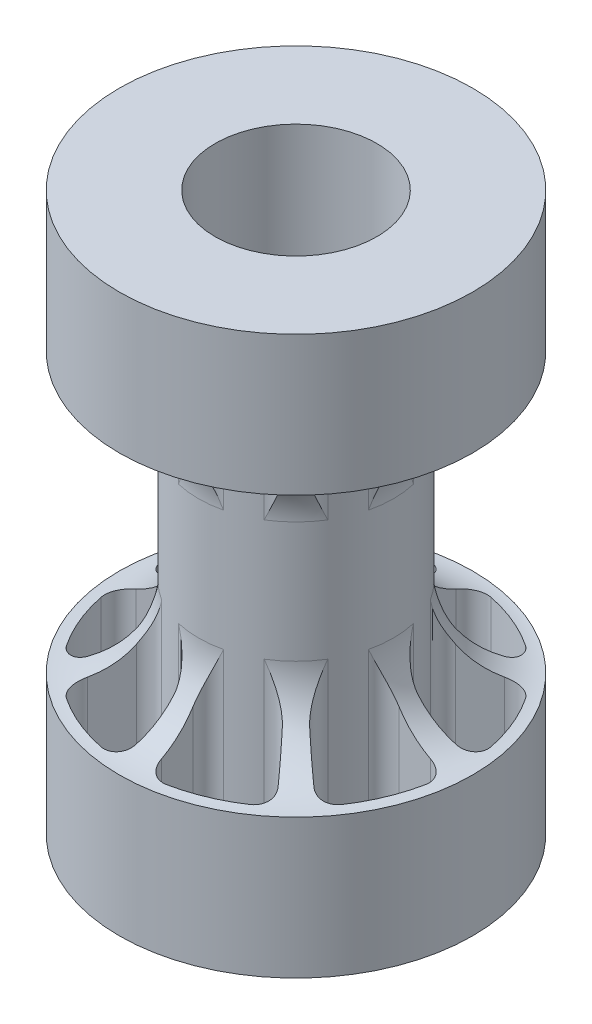
SolidWorks part; units mm, degrees
material "CA"
ref_plane "Front Plane" through (0, 0, 0) normal (0, 0, 1) x (1, 0, 0)
ref_plane "Top Plane" through (0, 0, 0) normal (0, 1, 0) x (1, 0, 0)
ref_plane "Right Plane" through (0, 0, 0) normal (1, 0, 0) x (0, 0, -1)
sketch "Sketch1" plane through (0, 0, 0) normal (0, 1, 0) x (1, 0, 0)
  circle A0 centre (0, 0) radius 14.5
  circle A1 centre (0, 0) radius 17.5
  dimension "D1" = 29
  dimension "D2" = 3
extrude "Boss-Extrude1" add sketch "Sketch1" along normal blind 100
sketch "Sketch2" plane through (0, 0, 0) normal (0, -1, 0) x (1, 0, 0)
  line L3 (-1.5, 17.4356) -> (-2.2728, 26.4182)
  line L6 (1.5, 17.4356) -> (2.2728, 26.4182)
  line L7 (11.2682, 13.3895) -> (17.0734, 20.2876)
  line L8 (13.3895, 11.2682) -> (20.2876, 17.0734)
  line L9 (17.4356, 1.5) -> (26.4182, 2.2728)
  line L10 (17.4356, -1.5) -> (26.4182, -2.2728)
  line L11 (13.3895, -11.2682) -> (20.2876, -17.0734)
  line L12 (11.2682, -13.3895) -> (17.0734, -20.2876)
  line L13 (1.5, -17.4356) -> (2.2728, -26.4182)
  line L14 (-1.5, -17.4356) -> (-2.2728, -26.4182)
  line L15 (-11.2682, -13.3895) -> (-17.0734, -20.2876)
  line L16 (-13.3895, -11.2682) -> (-20.2876, -17.0734)
  line L17 (-17.4356, -1.5) -> (-26.4182, -2.2728)
  line L18 (-17.4356, 1.5) -> (-26.4182, 2.2728)
  line L19 (-13.3895, 11.2682) -> (-20.2876, 17.0734)
  line L20 (-11.2682, 13.3895) -> (-17.0734, 20.2876)
  circle A0 centre (0, 0) radius 31.685
  arc A1 (-24.7173, 16.4395) -> (-29.1022, 5.8533) centre (0, 0) ccw
  circle A2 centre (0, 0) radius 17.5 construction
  arc A3 (-11.2682, 13.3895) -> (-13.3895, 11.2682) centre (0, 0) ccw
  arc A4 (1.5, 17.4356) -> (-1.5, 17.4356) centre (0, 0) ccw
  arc A5 (13.3895, 11.2682) -> (11.2682, 13.3895) centre (0, 0) ccw
  arc A6 (17.4356, -1.5) -> (17.4356, 1.5) centre (0, 0) ccw
  arc A7 (11.2682, -13.3895) -> (13.3895, -11.2682) centre (0, 0) ccw
  arc A8 (-1.5, -17.4356) -> (1.5, -17.4356) centre (0, 0) ccw
  arc A9 (-13.3895, -11.2682) -> (-11.2682, -13.3895) centre (0, 0) ccw
  arc A10 (-17.4356, 1.5) -> (-17.4356, -1.5) centre (0, 0) ccw
  arc A11 (-5.8533, 29.1022) -> (-16.4395, 24.7173) centre (0, 0) ccw
  arc A12 (16.4395, 24.7173) -> (5.8533, 29.1022) centre (0, 0) ccw
  arc A13 (29.1022, 5.8533) -> (24.7173, 16.4395) centre (0, 0) ccw
  arc A14 (24.7173, -16.4395) -> (29.1022, -5.8533) centre (0, 0) ccw
  arc A15 (5.8533, -29.1022) -> (16.4395, -24.7173) centre (0, 0) ccw
  arc A16 (-16.4395, -24.7173) -> (-5.8533, -29.1022) centre (0, 0) ccw
  arc A17 (-29.1022, -5.8533) -> (-24.7173, -16.4395) centre (0, 0) ccw
  arc A18 (26.4182, 2.2728) -> (29.1022, 5.8533) centre (26.1611, 5.2617) ccw
  arc A19 (26.4182, -2.2728) -> (29.1022, -5.8533) centre (26.1611, -5.2617) cw
  arc A20 (20.2876, -17.0734) -> (24.7173, -16.4395) centre (22.2193, -14.7781) ccw
  arc A21 (17.0734, -20.2876) -> (16.4395, -24.7173) centre (14.7781, -22.2193) cw
  arc A22 (2.2728, -26.4182) -> (5.8533, -29.1022) centre (5.2617, -26.1611) ccw
  arc A23 (-2.2728, -26.4182) -> (-5.8533, -29.1022) centre (-5.2617, -26.1611) cw
  arc A24 (-17.0734, -20.2876) -> (-16.4395, -24.7173) centre (-14.7781, -22.2193) ccw
  arc A25 (-20.2876, -17.0734) -> (-24.7173, -16.4395) centre (-22.2193, -14.7781) cw
  arc A26 (-26.4182, -2.2728) -> (-29.1022, -5.8533) centre (-26.1611, -5.2617) ccw
  arc A27 (-26.4182, 2.2728) -> (-29.1022, 5.8533) centre (-26.1611, 5.2617) cw
  arc A28 (-20.2876, 17.0734) -> (-24.7173, 16.4395) centre (-22.2193, 14.7781) ccw
  arc A29 (-17.0734, 20.2876) -> (-16.4395, 24.7173) centre (-14.7781, 22.2193) cw
  arc A30 (20.2876, 17.0734) -> (24.7173, 16.4395) centre (22.2193, 14.7781) cw
  arc A31 (17.0734, 20.2876) -> (16.4395, 24.7173) centre (14.7781, 22.2193) ccw
  arc A32 (2.2728, 26.4182) -> (5.8533, 29.1022) centre (5.2617, 26.1611) cw
  arc A33 (-2.2728, 26.4182) -> (-5.8533, 29.1022) centre (-5.2617, 26.1611) ccw
  point P41 (0, 0)
  point P49 (0, 0)
  point P72 (-2.5444, 29.5758)
  dimension "D1" = 63.37
  dimension "D2" = 2
  dimension "D6" = 3
  dimension "D3" = 1.5
  dimension "D4" = 1.5
  dimension "D5" = 8
extrude "Boss-Extrude2" add sketch "Sketch2" against normal up to surface (100 mm away) up to face at (0, 100, 17.5)
fillet "Fillet1" radius 3 16 edges at (-17.4356, 50, -1.5) (-13.3895, 50, -11.2682) (-11.2682, 50, -13.3895) (-1.5, 50, -17.4356) (1.5, 50, -17.4356) (11.2682, 50, -13.3895) (17.4356, 50, -1.5) (13.3895, 50, -11.2682) (13.3895, 50, 11.2682) (17.4356, 50, 1.5) (1.5, 50, 17.4356) (11.2682, 50, 13.3895) (-17.4356, 50, 1.5) (-13.3895, 50, 11.2682) (-11.2682, 50, 13.3895) (-1.5, 50, 17.4356)
sketch "Sketch7" plane through (0, 0, 0) normal (1, 0, 0) x (0, 0, -1)
  line L0 (-31.685, 75) -> (-31.685, 25)
  line L1 (-31.685, 100) -> (-31.685, 0) construction
  line L2 (-31.685, 100) -> (-31.685, 0) construction
  line L4 (-17.5, 39.185) -> (-17.5, 60.815)
  line L5 (0, 0) -> (0, 100) construction
  line L6 (31.685, 100) -> (-31.685, 100) construction
  arc A0 (-31.685, 25) -> (-17.5, 39.185) centre (-31.685, 39.185) ccw
  arc A1 (-31.685, 75) -> (-17.5, 60.815) centre (-31.685, 60.815) cw
  dimension "D1" = 25
  dimension "D2" = 25
  dimension "D3" = 17.5
revolve "Cut-Revolve2" cut sketch "Sketch7" angle 360 about L5
sketch "Sketch8" plane through (0, 100, 0) normal (0, 1, 0) x (1, 0, 0)
  circle A0 centre (0, 0) radius 31.685 construction
  circle A1 centre (0, 0) radius 31.685
  circle A2 centre (0, 0) radius 14.5 construction
  circle A3 centre (0, 0) radius 14.5
extrude "Boss-Extrude3" add sketch "Sketch8" against normal blind 2
fillet "Fillet2" radius 3 64 edges at (11.36, 98, -27.4254) (3.4624, 98, -28.5616) (2.0055, 98, -23.3115) (2.2963, 98, -18.1895) (6.697, 98, -16.1679) (11.2382, 98, -14.4856) (15.0656, 98, -17.9018) (17.7478, 98, -22.6443) (27.4254, 98, -11.36) (22.6443, 98, -17.7478) (17.9018, 98, -15.0656) (14.4856, 98, -11.2382) (16.1679, 98, -6.697) (18.1895, 98, -2.2963) (23.3115, 98, -2.0055) (28.5616, 98, -3.4624) (28.5616, 98, 3.4624) (23.3115, 98, 2.0055) (18.1895, 98, 2.2963) (16.1679, 98, 6.697) (14.4856, 98, 11.2382) (17.9018, 98, 15.0656) (22.6443, 98, 17.7478) (27.4254, 98, 11.36) (11.36, 98, 27.4254) (17.7478, 98, 22.6443) (15.0656, 98, 17.9018) (11.2382, 98, 14.4856) (6.697, 98, 16.1679) (2.2963, 98, 18.1895) (2.0055, 98, 23.3115) (3.4624, 98, 28.5616) (-11.36, 98, 27.4254) (-3.4624, 98, 28.5616) (-2.0055, 98, 23.3115) (-2.2963, 98, 18.1895) (-6.697, 98, 16.1679) (-11.2382, 98, 14.4856) (-15.0656, 98, 17.9018) (-17.7478, 98, 22.6443) (-27.4254, 98, 11.36) (-22.6443, 98, 17.7478) (-17.9018, 98, 15.0656) (-14.4856, 98, 11.2382) (-16.1679, 98, 6.697) (-18.1895, 98, 2.2963) (-23.3115, 98, 2.0055) (-28.5616, 98, 3.4624) (-27.4254, 98, -11.36) (-28.5616, 98, -3.4624) (-23.3115, 98, -2.0055) (-18.1895, 98, -2.2963) (-16.1679, 98, -6.697) (-14.4856, 98, -11.2382) (-17.9018, 98, -15.0656) (-22.6443, 98, -17.7478) (-11.36, 98, -27.4254) (-17.7478, 98, -22.6443) (-15.0656, 98, -17.9018) (-11.2382, 98, -14.4856) (-6.697, 98, -16.1679) (-2.2963, 98, -18.1895) (-2.0055, 98, -23.3115) (-3.4624, 98, -28.5616)
